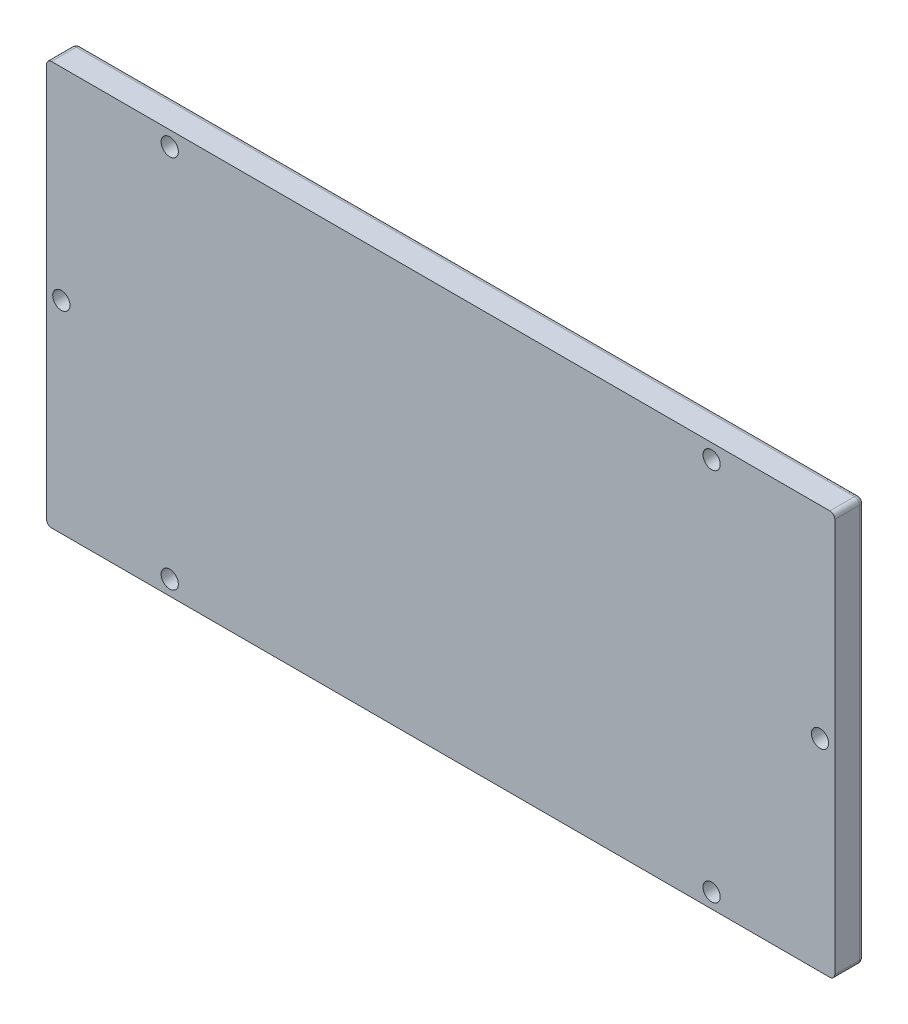
SolidWorks part; units mm, degrees
ref_plane "Plan de face" through (0, 0, 0) normal (0, 0, 1) x (1, 0, 0)
ref_plane "Plan de dessus" through (0, 0, 0) normal (0, 1, 0) x (1, 0, 0)
ref_plane "Plan de droite" through (0, 0, 0) normal (1, 0, 0) x (0, 0, -1)
sketch "Esquisse1" plane through (0, 0, 0) normal (0, 0, 1) x (1, 0, 0)
  line L1 (-80, -41) -> (80, -41)
  line L2 (-80, -41) -> (-80, 41)
  line L3 (-80, 41) -> (80, 41)
  line L4 (80, -41) -> (80, 41)
  line L5 (-80, -41) -> (80, 41) construction
  line L6 (-80, 41) -> (80, -41) construction
  point P0 (0, 0)
  dimension "D1" = 82
  dimension "D2" = 160
extrude "Boss.-Extru.1" add sketch "Esquisse1" along normal blind 6
sketch "Esquisse2" plane through (0, 0, 0) normal (0, 0, 1) x (1, 0, 0)
  line L0 (-81.9731, -38) -> (83.9393, -38) construction
  line L1 (-80, -41) -> (80, -41) construction
  line L2 (0, 0) -> (0, -49.9002) construction
  line L3 (-80, 41) -> (-80, -41) construction
  line L5 (-55, 38) -> (82.6895, 38) construction
  line L6 (80, 41) -> (-80, 41) construction
  circle A0 centre (-55, -38) radius 1.75
  circle A1 centre (55, -38) radius 1.75
  circle A2 centre (-55, 38) radius 1.75
  circle A3 centre (55, 38) radius 1.75
  dimension "D2" = 3.5
  dimension "D4" = 3
  dimension "D5" = 25
  dimension "D1" = 3
  dimension "D3" = 25
extrude "Enlèv. mat.-Extru.1" cut sketch "Esquisse2" along normal up to surface (6 mm away) up to face at (0, 0, 6)
sketch "Esquisse3" plane through (0, 0, 0) normal (0, 0, 1) x (1, 0, 0)
  line L0 (-84.0905, 0) -> (94.0725, 0) construction
  line L1 (77, 56.9426) -> (77, -50.5904) construction
  line L2 (80, -41) -> (80, 41) construction
  circle A0 centre (77, 0) radius 1.75
  dimension "D2" = 3.5
  dimension "D1" = 3
extrude "Enlèv. mat.-Extru.2" cut sketch "Esquisse3" along normal up to surface (6 mm away) up to face at (53.25, -38, 6)
mirror "Symétrie1" about plane through (0, 0, 0) normal (1, 0, 0) of "Enlèv. mat.-Extru.2"
sketch "Esquisse4" [suppressed] plane through (0, 0, 0) normal (0, 0, 1) x (1, 0, 0)
  line L0 (0, 0) -> (-33.7536, -51.4742) construction
  line L1 (-80, -41) -> (80, -41) construction
  line L2 (-49, -34) -> (9, -34)
  line L3 (-49, -34) -> (-49, -27)
  line L4 (-49, -27) -> (9, -27)
  line L5 (9, -34) -> (9, -27)
  line L6 (-49, -34) -> (9, -27) construction
  line L7 (-49, -27) -> (9, -34) construction
  line L8 (-80, 41) -> (-80, -41) construction
  point P3 (-20, -30.5)
  dimension "D1" = 7
  dimension "D2" = 7
  dimension "D3" = 58
  dimension "D4" = 31
extrude "Enlèv. mat.-Extru.3" [suppressed] cut sketch "Esquisse4" along normal up to surface (6 mm away)
sketch "Esquisse5" [suppressed] plane through (0, 0, 0) normal (0, 0, 1) x (1, 0, 0)
  line L1 (19.5, -34) -> (70, -34)
  line L2 (19.5, -34) -> (19.5, 0.5)
  line L3 (19.5, 0.5) -> (70, 0.5)
  line L4 (70, -34) -> (70, 0.5)
  line L5 (19.5, -34) -> (70, 0.5) construction
  line L6 (19.5, 0.5) -> (70, -34) construction
  line L7 (-49, -34) -> (9, -34) construction
  line L8 (80, -41) -> (80, 41) construction
  point P0 (44.75, -16.75)
  dimension "D1" = 50.5
  dimension "D2" = 34.5
  dimension "D3" = 10
extrude "Enlèv. mat.-Extru.4" [suppressed] cut sketch "Esquisse5" along normal up to surface (6 mm away)
sketch "Esquisse7" [suppressed] plane through (0, 0, 6) normal (0, 0, 1) x (1, 0, 0)
  line L0 (-19.9952, -2.2711) -> (-19.9952, 13.7289) construction
  line L1 (-27.4952, -2.2711) -> (-12.4952, -2.2711) construction
  line L2 (-27.4952, -2.2711) -> (-27.4952, 7.7289) construction
  line L3 (-27.4952, 7.7289) -> (-12.4952, 7.7289) construction
  line L4 (-12.4952, -2.2711) -> (-12.4952, 7.7289) construction
  line L5 (-27.4952, -2.2711) -> (-12.4952, 7.7289) construction
  line L6 (-27.4952, 7.7289) -> (-12.4952, -2.2711) construction
  line L7 (-23.4952, -2.2711) -> (-23.4952, 13.7289)
  line L8 (-16.4952, -2.2711) -> (-16.4952, 13.7289)
  line L9 (-80, 41) -> (-80, -41) construction
  line L10 (80, 41) -> (-80, 41) construction
  arc A1 (-23.4952, -2.2711) -> (-16.4952, -2.2711) centre (-19.9952, -2.2711) ccw
  arc A2 (-16.4952, 13.7289) -> (-23.4952, 13.7289) centre (-19.9952, 13.7289) ccw
  circle A3 centre (-27.4952, -2.2711) radius 1.5
  circle A4 centre (-12.4952, -2.2711) radius 1.5
  point P6 (-19.9952, 5.7289)
  dimension "D1" = 3.5
  dimension "D2" = 16
  dimension "D4" = 3
  dimension "D6" = 27.2711
  dimension "D3" = 15
  dimension "D5" = 56.5048
extrude "Enlèv. mat.-Extru.5" [suppressed] cut sketch "Esquisse7" against normal up to surface (6 mm away)
fillet "Congé1" [suppressed] radius 1
fillet "Congé2" radius 1 14 edges at (0, 41, 0) (-80, 0, 0) (0, -41, 0) (80, 0, 0) (-53.25, -38, 0) (56.75, 38, 0) (-53.25, 38, 0) (56.75, -38, 0) (78.75, 0, 0) (-78.75, 0, 0) (80, 41, 3) (80, -41, 3) (-80, -41, 3) (-80, 41, 3)
